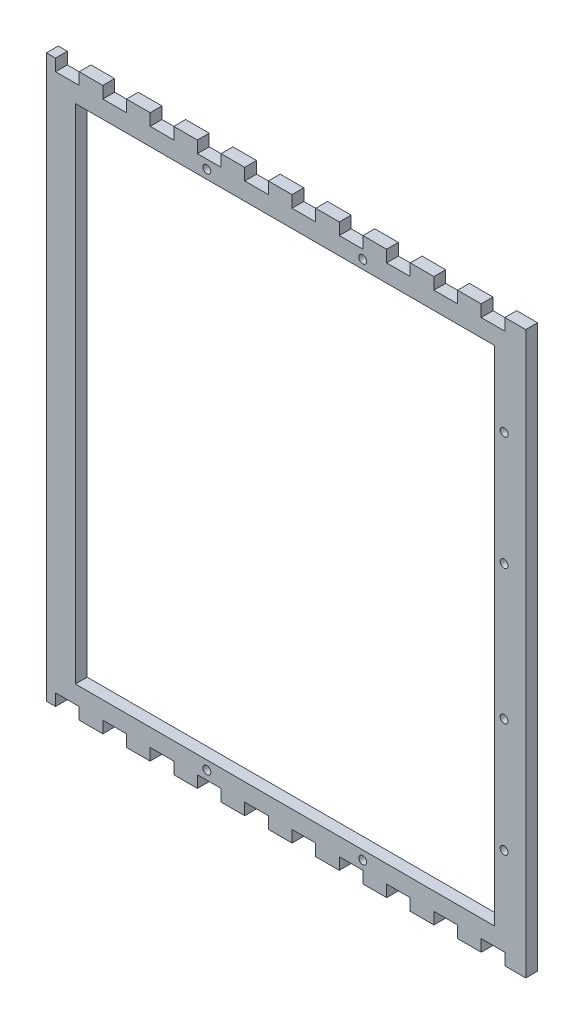
SolidWorks part; units mm, degrees
ref_plane "Front Plane" through (0, 0, 0) normal (0, 0, 1) x (1, 0, 0)
ref_plane "Top Plane" through (0, 0, 0) normal (0, 1, 0) x (1, 0, 0)
ref_plane "Right Plane" through (0, 0, 0) normal (1, 0, 0) x (0, 0, -1)
sketch "Model" plane through (0, 0, 0) normal (0, 0, 1) x (1, 0, 0)
  line L857 (1148.22, 22.8575) -> (1152.62, 22.8575)
  line L858 (1152.62, 22.8575) -> (1152.62, 28.5722)
  line L859 (1152.62, 28.5722) -> (1164.05, 28.5722)
  line L860 (1164.05, 28.5722) -> (1164.05, 22.8575)
  line L861 (1164.05, 22.8575) -> (1175.48, 22.8575)
  line L862 (1175.48, 22.8575) -> (1175.48, 28.5722)
  line L863 (1175.48, 28.5722) -> (1186.91, 28.5722)
  line L864 (1186.91, 28.5722) -> (1186.91, 22.8575)
  line L865 (1186.91, 22.8575) -> (1198.34, 22.8575)
  line L866 (1198.34, 22.8575) -> (1198.34, 28.5722)
  line L867 (1198.34, 28.5722) -> (1209.77, 28.5722)
  line L868 (1209.77, 28.5722) -> (1209.77, 22.8575)
  line L869 (1209.77, 22.8575) -> (1221.2, 22.8575)
  line L870 (1221.2, 22.8575) -> (1221.2, 28.5722)
  line L871 (1221.2, 28.5722) -> (1232.63, 28.5722)
  line L872 (1232.63, 28.5722) -> (1232.63, 22.8575)
  line L873 (1232.63, 22.8575) -> (1244.06, 22.8575)
  line L874 (1244.06, 22.8575) -> (1244.06, 28.5722)
  line L875 (1244.06, 28.5722) -> (1255.49, 28.5722)
  line L876 (1255.49, 28.5722) -> (1255.49, 22.8575)
  line L877 (1255.49, 22.8575) -> (1266.92, 22.8575)
  line L878 (1266.92, 22.8575) -> (1266.92, 28.5722)
  line L879 (1266.92, 28.5722) -> (1278.35, 28.5722)
  line L880 (1278.35, 28.5722) -> (1278.35, 22.8575)
  line L881 (1278.35, 22.8575) -> (1289.78, 22.8575)
  line L882 (1289.78, 22.8575) -> (1289.78, 28.5722)
  line L883 (1289.78, 28.5722) -> (1301.21, 28.5722)
  line L884 (1301.21, 28.5722) -> (1301.21, 22.8575)
  line L885 (1301.21, 22.8575) -> (1312.64, 22.8575)
  line L886 (1312.64, 22.8575) -> (1312.64, 28.5722)
  line L887 (1312.64, 28.5722) -> (1324.07, 28.5722)
  line L888 (1324.07, 28.5722) -> (1324.07, 22.8575)
  line L889 (1324.07, 22.8575) -> (1335.5, 22.8575)
  line L890 (1335.5, 22.8575) -> (1335.5, 28.5722)
  line L891 (1335.5, 28.5722) -> (1346.93, 28.5722)
  line L892 (1346.93, 28.5722) -> (1346.93, 22.8575)
  line L893 (1346.93, 22.8575) -> (1358.36, 22.8575)
  line L894 (1358.36, 22.8575) -> (1358.36, 28.5722)
  line L895 (1358.36, 28.5722) -> (1369.79, 28.5722)
  line L896 (1369.79, 28.5722) -> (1369.79, 22.8575)
  line L897 (1369.79, 22.8575) -> (1374.18, 22.8575)
  line L898 (1374.18, 22.8575) -> (1379.9, 22.8575)
  line L899 (1379.9, 22.8575) -> (1379.9, 28.5722)
  line L900 (1379.9, 28.5722) -> (1379.9, 288.572)
  line L901 (1379.9, 288.572) -> (1379.9, 294.287)
  line L902 (1379.9, 294.287) -> (1374.18, 294.287)
  line L903 (1374.18, 294.287) -> (1369.79, 294.287)
  line L904 (1369.79, 294.287) -> (1369.79, 288.572)
  line L905 (1369.79, 288.572) -> (1358.36, 288.572)
  line L906 (1358.36, 288.572) -> (1358.36, 294.287)
  line L907 (1358.36, 294.287) -> (1346.93, 294.287)
  line L908 (1346.93, 294.287) -> (1346.93, 288.572)
  line L909 (1346.93, 288.572) -> (1335.5, 288.572)
  line L910 (1335.5, 288.572) -> (1335.5, 294.287)
  line L911 (1335.5, 294.287) -> (1324.07, 294.287)
  line L912 (1324.07, 294.287) -> (1324.07, 288.572)
  line L913 (1324.07, 288.572) -> (1312.64, 288.572)
  line L914 (1312.64, 288.572) -> (1312.64, 294.287)
  line L915 (1312.64, 294.287) -> (1301.21, 294.287)
  line L916 (1301.21, 294.287) -> (1301.21, 288.572)
  line L917 (1301.21, 288.572) -> (1289.78, 288.572)
  line L918 (1289.78, 288.572) -> (1289.78, 294.287)
  line L919 (1289.78, 294.287) -> (1278.35, 294.287)
  line L920 (1278.35, 294.287) -> (1278.35, 288.572)
  line L921 (1278.35, 288.572) -> (1266.92, 288.572)
  line L922 (1266.92, 288.572) -> (1266.92, 294.287)
  line L923 (1266.92, 294.287) -> (1255.49, 294.287)
  line L924 (1255.49, 294.287) -> (1255.49, 288.572)
  line L925 (1255.49, 288.572) -> (1244.06, 288.572)
  line L926 (1244.06, 288.572) -> (1244.06, 294.287)
  line L927 (1244.06, 294.287) -> (1232.63, 294.287)
  line L928 (1232.63, 294.287) -> (1232.63, 288.572)
  line L929 (1232.63, 288.572) -> (1221.2, 288.572)
  line L930 (1221.2, 288.572) -> (1221.2, 294.287)
  line L931 (1221.2, 294.287) -> (1209.77, 294.287)
  line L932 (1209.77, 294.287) -> (1209.77, 288.572)
  line L933 (1209.77, 288.572) -> (1198.34, 288.572)
  line L934 (1198.34, 288.572) -> (1198.34, 294.287)
  line L935 (1198.34, 294.287) -> (1186.91, 294.287)
  line L936 (1186.91, 294.287) -> (1186.91, 288.572)
  line L937 (1186.91, 288.572) -> (1175.48, 288.572)
  line L938 (1175.48, 288.572) -> (1175.48, 294.287)
  line L939 (1175.48, 294.287) -> (1164.05, 294.287)
  line L940 (1164.05, 294.287) -> (1164.05, 288.572)
  line L941 (1164.05, 288.572) -> (1152.62, 288.572)
  line L942 (1152.62, 288.572) -> (1152.62, 294.287)
  line L943 (1152.62, 294.287) -> (1148.22, 294.287)
  line L944 (1148.22, 294.287) -> (1148.22, 288.572)
  line L945 (1148.22, 288.572) -> (1148.22, 28.5722)
  line L946 (1148.22, 28.5722) -> (1148.22, 22.8575)
extrude "Boss-Extrude1" add sketch "Model" along normal blind 5.715
sketch "Sketch1" plane through (0, 0, 0) normal (0, 0, -1) x (-1, 0, 0)
  line L8 (-1162.185, 280.0719) -> (-1364.685, 280.0719)
  line L9 (-1162.185, 37.0719) -> (-1162.185, 280.0719)
  line L10 (-1364.685, 37.0719) -> (-1162.185, 37.0719)
  line L11 (-1364.685, 280.0719) -> (-1364.685, 37.0719)
  line L12 (-1162.185, 280.0719) -> (-1364.685, 280.0719)
  line L13 (-1162.185, 37.0719) -> (-1162.185, 280.0719)
  line L14 (-1364.685, 37.0719) -> (-1162.185, 37.0719)
  line L15 (-1364.685, 280.0719) -> (-1364.685, 37.0719)
  dimension "D1" = 0.5
extrude "Cut-Extrude1" cut sketch "Sketch1" against normal through all
sketch "Sketch2" plane through (0, 0, 0) normal (0, 0, -1) x (-1, 0, 0)
  line L0 (-1364.075, 288.572) -> (-1364.075, 280.0719) construction
  line L1 (-1369.79, 288.572) -> (-1358.36, 288.572) construction
  line L2 (-1162.185, 280.0719) -> (-1364.685, 280.0719) construction
  line L3 (-1379.9, 284.322) -> (-1148.22, 284.322) construction
  line L4 (-1379.9, 22.8575) -> (-1379.9, 294.287) construction
  line L5 (-1148.22, 294.287) -> (-1148.22, 22.8575) construction
  line L6 (-1379.9, 158.5722) -> (-1148.22, 158.5722) construction
  line L7 (-1263.435, 271.0719) -> (-1263.435, 284.322) construction
  line L8 (-1340.435, 271.5844) -> (-1291.1017, 271.5844) construction
  line L9 (-1340.435, 277.572) -> (-1340.435, 264.572) construction
  line L10 (-1291.1017, 277.572) -> (-1291.1017, 264.572) construction
  line L11 (-1301.1017, 271.5844) -> (-1301.1017, 284.322) construction
  point P6 (-1364.075, 284.322)
  point P15 (-1301.1017, 284.322)
  point P31 (-1225.7683, 284.322)
  point P32 (-1225.7683, 32.8225)
  point P34 (-1301.1017, 32.8225)
  dimension "D1" = 10
hole_wizard "CSK for #6 Flat Head Machine Screw (100)1" positions "Sketch3" profile "Sketch4" countersink size "#6" standard "ANSI Inch" end condition through all
sketch "Sketch3" plane through (0, 0, 0) normal (0, 0, -1) x (-1, 0, 0)
  point P0 (-1301.1017, 284.322)
  point P3 (-1225.7683, 284.322)
  point P6 (-1225.7683, 32.8225)
  point P9 (-1301.1017, 32.8225)
sketch "Sketch4" plane through (1301.1017, 284.322, 0) normal (1, 0, 0) x (0, 1, 0)
  line L0 (0, 0) -> (0, 5.715)
  line L1 (0, 5.715) -> (1.8986, 5.715)
  line L2 (1.8986, 5.715) -> (1.8986, 1.38)
  line L3 (1.8986, 1.38) -> (3.5433, 0)
  line L5 (3.5433, 0) -> (0, 0)
  line L6 (-1.8986, 1.38) -> (-3.5433, 0) construction
  line L11 (0, -6.35) -> (0, 107.95) construction
  dimension "Thru Hole Dia." = 3.7973
  dimension "Thru Hole Depth" = 5.715
  dimension "Near C'Sink Dia." = 7.0866
  dimension "Near C'Sink Angle" = 100
sketch "Sketch5" plane through (0, 0, 0) normal (0, 0, -1) x (-1, 0, 0)
  point P0 (-1369.435, 246.0721)
  point P1 (-1369.435, 191.0721)
  point P3 (-1369.435, 71.0721)
  point P5 (-1369.435, 126.0721)
hole_wizard "CSK for #6 Flat Head Machine Screw (100)2" positions "Sketch6" profile "Sketch7" countersink size "#6" standard "ANSI Inch" end condition through all
sketch "Sketch6" plane through (0, 0, 0) normal (0, 0, -1) x (-1, 0, 0)
  point P0 (-1369.435, 246.0721)
  point P3 (-1369.435, 191.0721)
  point P6 (-1369.435, 126.0721)
  point P9 (-1369.435, 71.0721)
sketch "Sketch7" plane through (1369.435, 246.0721, 0) normal (1, 0, 0) x (0, 1, 0)
  line L0 (0, 0) -> (0, 5.715)
  line L1 (0, 5.715) -> (1.8986, 5.715)
  line L2 (1.8986, 5.715) -> (1.8986, 1.38)
  line L3 (1.8986, 1.38) -> (3.5433, 0)
  line L5 (3.5433, 0) -> (0, 0)
  line L6 (-1.8986, 1.38) -> (-3.5433, 0) construction
  line L11 (0, -6.35) -> (0, 107.95) construction
  dimension "Thru Hole Dia." = 3.7973
  dimension "Thru Hole Depth" = 5.715
  dimension "Near C'Sink Dia." = 7.0866
  dimension "Near C'Sink Angle" = 100
